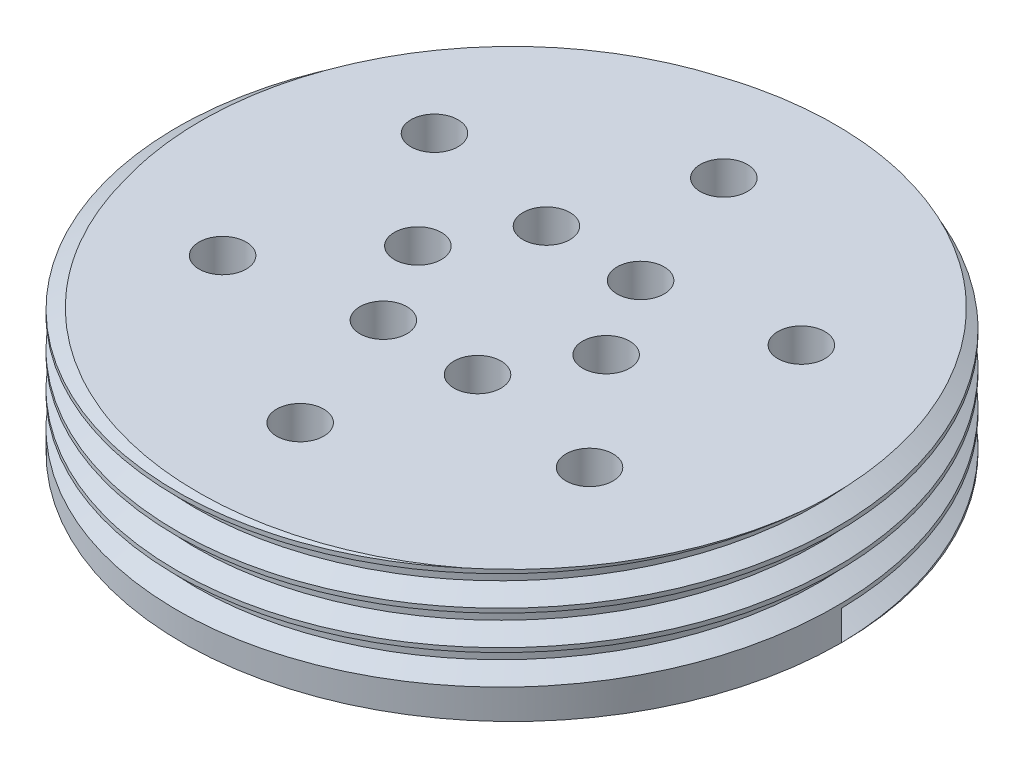
SolidWorks part; units mm, degrees
ref_plane "Front Plane" through (0, 0, 0) normal (0, 0, 1) x (1, 0, 0)
ref_plane "Top Plane" through (0, 0, 0) normal (0, 1, 0) x (1, 0, 0)
ref_plane "Right Plane" through (0, 0, 0) normal (1, 0, 0) x (0, 0, -1)
sketch "Sketch2" plane through (0, 0, 0) normal (0, 1, 0) x (1, 0, 0)
  line L0 (-19.4856, 11.25) -> (0, 0) construction
  line L1 (-5, 8.6603) -> (0, 0) construction
  line L2 (0, 22.5) -> (0, 0) construction
  circle A0 centre (0, 0) radius 35
  circle A1 centre (0, 0) radius 22.5
  circle A2 centre (0, 22.5) radius 2.5
  circle A3 centre (19.4856, 11.25) radius 2.5
  circle A4 centre (19.4856, -11.25) radius 2.5
  circle A5 centre (0, -22.5) radius 2.5
  circle A6 centre (-19.4856, -11.25) radius 2.5
  circle A7 centre (-19.4856, 11.25) radius 2.5
  circle A8 centre (0, 0) radius 10
  circle A10 centre (-5, 8.6603) radius 2.5
  circle A11 centre (5, 8.6603) radius 2.5
  circle A12 centre (10, 0) radius 2.5
  circle A13 centre (5, -8.6603) radius 2.5
  circle A14 centre (-5, -8.6603) radius 2.5
  circle A15 centre (-10, 0) radius 2.5
  point P18 (0, 0)
  point P32 (0, 0)
  dimension "D1" = 70
  dimension "D2" = 45
  dimension "D3" = 5
  dimension "D5" = 20
  dimension "D6" = 30
  dimension "D8" = 5
  dimension "D7" = 30
  dimension "D4" = 6
  dimension "D9" = 6
extrude "Boss-Extrude1" add sketch "Sketch2" along normal blind 14 contours A0 A7 A1 A2 A3 A4 A5 A6 | A7 A1 A6 A5 A4 A3 A2 A15 A8 A10 A11 A12 A13 A14 | A15 A8 A14 A13 A12 A11 A10 region at (-34.0101, 0, 0) region at (21.4023, 0, 4.4771) region at (0, 0, 0)
thread "Thread1" pitch 3.6286 method cut profile "Thread Profile1" start angle 0, offset 0, length 15, pitch 3.6286, diameter 70
ref_plane "Plane1" through (35, 0, 0) normal (0, 0, 1) x (1, 0, 0)
sketch "Thread Profile1" plane through (35, 0, 0) normal (0, 0, 1) x (1, 0, 0)
  line L0 (0, 0) -> (0, 3.6286) construction
  line L11 (0, 0) -> (0, 3.175)
  line L12 (0, 3.175) -> (-1.964, 2.0411)
  line L13 (-1.964, 2.0411) -> (-1.964, 1.1339)
  line L15 (-1.964, 1.1339) -> (0, 0)
  line L17 (-1.964, 1.5875) -> (0, 1.5875) construction
  point P2 (0, 0)
  dimension "Pitch" = 3.6286
  dimension "Profile_Angle" = 60
  dimension "Profile_Land" = 0.9071
  dimension "Profile_Height" = 1.964
